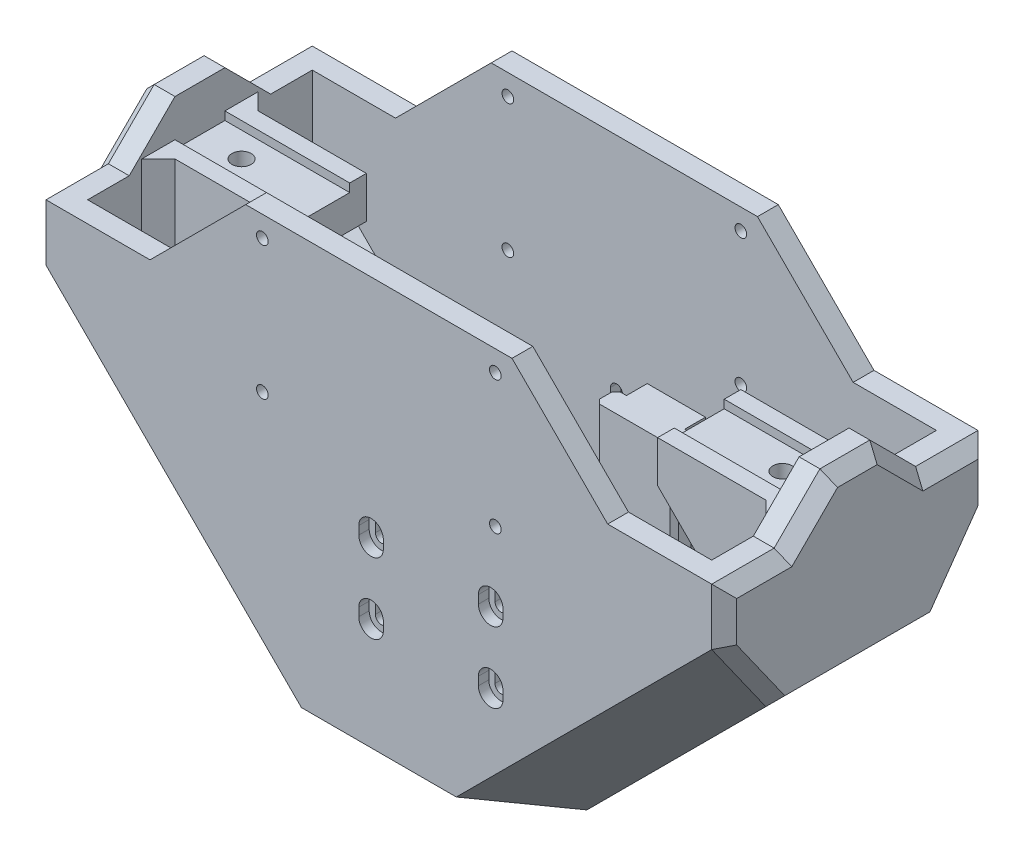
SolidWorks part; units mm, degrees
ref_plane "Front Plane" through (0, 0, 0) normal (0, 0, 1) x (1, 0, 0)
ref_plane "Top Plane" through (0, 0, 0) normal (0, 1, 0) x (1, 0, 0)
ref_plane "Right Plane" through (0, 0, 0) normal (1, 0, 0) x (0, 0, -1)
sketch "Sketch1" plane through (0, 0, 0) normal (0, 1, 0) x (1, 0, 0)
  line L1 (-75, -27) -> (75, -27)
  line L2 (-75, -27) -> (-75, 27)
  line L3 (-75, 27) -> (75, 27)
  line L4 (75, -27) -> (75, 27)
  line L5 (-75, -27) -> (75, 27) construction
  line L6 (-75, 27) -> (75, -27) construction
  point P0 (0, 0)
  dimension "D1" = 150
  dimension "D2" = 54
extrude "Boss-Extrude1" add sketch "Sketch1" along normal blind 70
shell "Shell1" thickness 5
sketch "Sketch2" plane through (80, 0, 0) normal (1, 0, 0) x (0, 0, -1)
  line L0 (-17, 70) -> (-6, 81)
  line L1 (-32, 70) -> (32, 70) construction
  line L2 (-6, 81) -> (6, 81)
  line L3 (6, 81) -> (17, 70)
  line L4 (17, 70) -> (-17, 70)
  line L5 (0, 81) -> (0, 75) construction
  dimension "D1" = 11
  dimension "D2" = 45
  dimension "D3" = 45
  dimension "D4" = 12
extrude "Boss-Extrude2" add sketch "Sketch2" against normal blind 5
sketch "Sketch4" plane through (0, 0, -32) normal (0, 0, -1) x (-1, 0, 0)
  line L0 (-55, 70) -> (-32, 93)
  line L1 (-80, 70) -> (80, 70) construction
  line L2 (-32, 93) -> (32, 93)
  line L3 (32, 93) -> (55, 70)
  line L4 (55, 70) -> (-55, 70)
  line L5 (0, 93) -> (0, 70) construction
  line L6 (-80, 70) -> (-80, -5) construction
  dimension "D1" = 23
  dimension "D2" = 25
  dimension "D3" = 45
extrude "Boss-Extrude3" add sketch "Sketch4" against normal blind 5
sketch "Sketch3" plane through (0, 0, -32) normal (0, 0, -1) x (-1, 0, 0)
  line L1 (-28, 56) -> (28, 56) construction
  line L2 (-28, 56) -> (-28, 88) construction
  line L3 (-28, 88) -> (28, 88) construction
  line L4 (28, 56) -> (28, 88) construction
  line L5 (-28, 56) -> (28, 88) construction
  line L6 (-28, 88) -> (28, 56) construction
  line L7 (32, 93) -> (-32, 93) construction
  circle A0 centre (-28, 88) radius 1.4
  circle A1 centre (-28, 56) radius 1.4
  circle A2 centre (28, 88) radius 1.4
  circle A3 centre (28, 56) radius 1.4
  point P0 (0, 72)
  dimension "D1" = 2.8
  dimension "D2" = 56
  dimension "D3" = 32
  dimension "D4" = 5
extrude "Cut-Extrude1" cut sketch "Sketch3" against normal blind 6
mirror "Mirror4" about plane through (0, 0, 0) normal (0, 0, 1) of "Boss-Extrude3", "Cut-Extrude1"
mirror "Mirror5" about plane through (0, 0, 0) normal (1, 0, 0) of "Boss-Extrude2"
sketch "Sketch5" plane through (0, 0, 0) normal (0, 0, 1) x (1, 0, 0)
  line L0 (-75, 70) -> (-45, 70)
  line L1 (-45, 70) -> (-45, 62)
  line L2 (-45, 62) -> (-75, 32)
  line L4 (-75, 32) -> (-75, 70)
  line L5 (-75, 81) -> (-75, 70) construction
  line L6 (-80, 70) -> (-55, 70) construction
  dimension "D1" = 30
  dimension "D2" = 8
  dimension "D3" = 45
extrude "Boss-Extrude4" add sketch "Sketch5" along normal mid plane 20
sketch "Sketch9" plane through (0, 70, 0) normal (0, 1, 0) x (1, 0, 0)
  line L4 (-45, 10) -> (-75, 10)
  line L5 (-75, 10) -> (-75, -10)
  line L6 (-75, -10) -> (-45, -10)
  line L7 (-45, -10) -> (-45, 10)
  line L8 (-45, 10) -> (-75, 10)
  line L10 (-75, -10) -> (-45, -10)
  line L11 (-45, -10) -> (-45, 10)
  line L13 (-75, 10) -> (-75, -10)
  dimension "D1" = 0
extrude "Boss-Extrude6" add sketch "Sketch9" along normal blind 2
sketch "Sketch10" plane through (-75, 0, 0) normal (1, 0, 0) x (0, 0, -1)
  line L0 (-10, 72) -> (10, 72) construction
  line L1 (-6, 72) -> (6, 72)
  line L2 (-6, 72) -> (-6, 70)
  line L3 (-6, 70) -> (6, 70)
  line L4 (6, 72) -> (6, 70)
  line L5 (-6, 72) -> (6, 70) construction
  line L6 (-6, 70) -> (6, 72) construction
  point P0 (0, 71)
  dimension "D1" = 2
  dimension "D2" = 12
extrude "Cut-Extrude2" cut sketch "Sketch10" along normal up to next
sketch "Sketch11" plane through (0, 70, 0) normal (0, 1, 0) x (1, 0, 0)
  line L1 (-75, 6) -> (-75, -6) construction
  circle A0 centre (-65, 0) radius 2.3
  dimension "D1" = 4.6
  dimension "D2" = 10
extrude "Cut-Extrude3" cut sketch "Sketch11" against normal blind 6
mirror "Mirror24" about plane through (0, 0, 0) normal (1, 0, 0) of "Cut-Extrude2", "Boss-Extrude4", "Boss-Extrude6", "Cut-Extrude3"
chamfer "Chamfer3" distance 40 angle 45 2 edges at (75, 0, 0) (-75, 0, 0)
chamfer "Chamfer5" distance 43 angle 45 2 edges at (-80, -5, 0) (80, -5, 0)
chamfer "Chamfer11" distance 10 angle 45 4 edges at (55, 20, 27) (55, 20, -27) (-55, 20, -27) (-55, 20, 27)
chamfer "Chamfer12" distance 13 angle 45 4 edges at (-58.5, 16.5, -32) (58.5, 16.5, -32) (-58.5, 16.5, 32) (58.5, 16.5, 32)
chamfer "Chamfer13" distance 4 angle 45 8 edges at (-75, 56, -10) (-75, 56, 10) (75, 56, 10) (75, 56, -10) (73, 38, -10) (73, 38, 10) (-73, 38, 10) (-73, 38, -10)
sketch "Sketch16" plane through (80, 0, 0) normal (1, 0, 0) x (0, 0, -1)
  line L10 (-19, 38) -> (19, 38)
  line L11 (19, 38) -> (32, 56.3848)
  line L12 (32, 56.3848) -> (32, 70)
  line L13 (32, 70) -> (17, 70)
  line L14 (17, 70) -> (6, 81)
  line L15 (6, 81) -> (-6, 81)
  line L16 (-6, 81) -> (-17, 70)
  line L17 (-17, 70) -> (-32, 70)
  line L18 (-32, 70) -> (-32, 56.3848)
  line L19 (-32, 56.3848) -> (-19, 38)
  line L20 (-19, 38) -> (19, 38)
  line L21 (19, 38) -> (32, 56.3848)
  line L22 (32, 56.3848) -> (32, 70)
  line L23 (32, 70) -> (17, 70)
  line L24 (17, 70) -> (6, 81)
  line L25 (6, 81) -> (-6, 81)
  line L26 (-6, 81) -> (-17, 70)
  line L27 (-17, 70) -> (-32, 70)
  line L28 (-32, 70) -> (-32, 56.3848)
  line L29 (-32, 56.3848) -> (-19, 38)
  dimension "D1" = 0
extrude "Boss-Extrude10" add sketch "Sketch16" along normal blind 3
chamfer "Chamfer14" distance 3 angle 45 10 edges at (83, 63.1924, 32) (83, 70, 24.5) (83, 75.5, 11.5) (83, 81, 0) (83, 75.5, -11.5) (83, 70, -24.5) (83, 63.1924, -32) (83, 47.1924, -25.5) (83, 38, 0) (83, 47.1924, 25.5)
mirror "Mirror28" about plane through (0, 0, 0) normal (1, 0, 0) of "Chamfer14", "Boss-Extrude10"
sketch "Sketch17" plane through (0, 0, 0) normal (0, 1, 0) x (1, 0, 0)
  line L0 (-32, -27) -> (32, -27) construction
  line L1 (5.5, -27) -> (19.5, -27)
  line L2 (5.5, -27) -> (5.5, -22)
  line L3 (5.5, -22) -> (19.5, -22)
  line L4 (19.5, -27) -> (19.5, -22)
  line L5 (5.5, -27) -> (19.5, -22) construction
  line L6 (5.5, -22) -> (19.5, -27) construction
  line L7 (3, -22) -> (22, -22)
  line L8 (3, -22) -> (3, -17)
  line L9 (3, -17) -> (22, -17)
  line L10 (22, -22) -> (22, -17)
  line L11 (3, -22) -> (22, -17) construction
  line L12 (3, -17) -> (22, -22) construction
  point P0 (12.5, -24.5)
  point P5 (12.5, -19.5)
  line M10 (-20.8579, -27) -> (20.8579, -27)
  dimension "D1" = 19
  dimension "D2" = 14
  dimension "D3" = 5
  dimension "D4" = 12.5
extrude "Boss-Extrude11" add sketch "Sketch17" along normal blind 45 contours L7 L10 L9 L8 L3 | L4 L3 L2 M10
sketch "Sketch20" plane through (0, 0, 0) normal (0, 1, 0) x (1, 0, 0)
  line L0 (22, -22) -> (22, -17) construction
  line L1 (3, -17) -> (22, -17)
  line L2 (3, -17) -> (3, -12)
  line L3 (3, -12) -> (22, -12)
  line L4 (22, -17) -> (22, -12)
  dimension "D1" = 5
extrude "Boss-Extrude14" add sketch "Sketch20" along normal blind 8
mirror "Mirror29" about plane through (0, 0, 0) normal (0, 0, 1) of "Boss-Extrude14", "Boss-Extrude11"
sketch "Sketch22" plane through (0, 0, -27) normal (0, 0, 1) x (1, 0, 0)
  line L0 (5.5, 0) -> (-20.8579, 0) construction
  line L1 (-1.875, 21.8) -> (26.875, 21.8) construction
  line L2 (-1.875, 21.8) -> (-1.875, 38.8) construction
  line L3 (-1.875, 38.8) -> (26.875, 38.8) construction
  line L4 (26.875, 21.8) -> (26.875, 38.8) construction
  line L5 (-1.875, 21.8) -> (26.875, 38.8) construction
  line L6 (-1.875, 38.8) -> (26.875, 21.8) construction
  line L7 (3, 45) -> (22, 45) construction
  line L8 (-1.875, 37.8) -> (-1.875, 39.8) construction
  line L9 (-3.325, 37.8) -> (-3.325, 39.8)
  line L10 (-0.425, 37.8) -> (-0.425, 39.8)
  line L11 (12.5, 38.8) -> (12.5, 30.3) construction
  line L12 (12.5, 30.3) -> (-1.875, 30.3) construction
  line L13 (26.875, 37.8) -> (26.875, 39.8) construction
  line L14 (28.325, 37.8) -> (28.325, 39.8)
  line L15 (25.425, 37.8) -> (25.425, 39.8)
  line L16 (-1.875, 22.8) -> (-1.875, 20.8) construction
  line L17 (-3.325, 22.8) -> (-3.325, 20.8)
  line L18 (-0.425, 22.8) -> (-0.425, 20.8)
  line L19 (26.875, 22.8) -> (26.875, 20.8) construction
  line L20 (28.325, 22.8) -> (28.325, 20.8)
  line L21 (25.425, 22.8) -> (25.425, 20.8)
  arc A4 (-3.325, 37.8) -> (-0.425, 37.8) centre (-1.875, 37.8) ccw
  arc A5 (-0.425, 39.8) -> (-3.325, 39.8) centre (-1.875, 39.8) ccw
  arc A6 (28.325, 37.8) -> (25.425, 37.8) centre (26.875, 37.8) cw
  arc A7 (25.425, 39.8) -> (28.325, 39.8) centre (26.875, 39.8) cw
  arc A8 (-3.325, 22.8) -> (-0.425, 22.8) centre (-1.875, 22.8) cw
  arc A9 (-0.425, 20.8) -> (-3.325, 20.8) centre (-1.875, 20.8) cw
  arc A10 (28.325, 22.8) -> (25.425, 22.8) centre (26.875, 22.8) ccw
  arc A11 (25.425, 20.8) -> (28.325, 20.8) centre (26.875, 20.8) ccw
  point P0 (12.5, 30.3)
  point P7 (12.5, 45)
  point P11 (-1.875, 38.8)
  point P22 (26.875, 38.8)
  point P29 (-1.875, 21.8)
  point P36 (26.875, 21.8)
  dimension "D4" = 1.45
  dimension "D1" = 21.8
  dimension "D2" = 28.75
  dimension "D3" = 17
  dimension "D5" = 2
extrude "Cut-Extrude4" cut sketch "Sketch22" against normal blind 2.5
sketch "Sketch23" plane through (0, 0, -29.5) normal (0, 0, 1) x (1, 0, 0)
  line L6 (29.825, 37.8) -> (29.825, 39.8)
  line L7 (23.925, 39.8) -> (23.925, 37.8)
  line L8 (29.825, 37.8) -> (29.825, 39.8)
  line L9 (23.925, 39.8) -> (23.925, 37.8)
  line L12 (1.075, 37.8) -> (1.075, 39.8)
  line L13 (-4.825, 39.8) -> (-4.825, 37.8)
  line L14 (1.075, 37.8) -> (1.075, 39.8)
  line L15 (-4.825, 39.8) -> (-4.825, 37.8)
  line L18 (-4.825, 22.8) -> (-4.825, 20.8)
  line L19 (1.075, 20.8) -> (1.075, 22.8)
  line L20 (-4.825, 22.8) -> (-4.825, 20.8)
  line L21 (1.075, 20.8) -> (1.075, 22.8)
  line L24 (23.925, 22.8) -> (23.925, 20.8)
  line L25 (29.825, 20.8) -> (29.825, 22.8)
  line L26 (23.925, 22.8) -> (23.925, 20.8)
  line L27 (29.825, 20.8) -> (29.825, 22.8)
  arc A6 (23.925, 37.8) -> (29.825, 37.8) centre (26.875, 37.8) ccw
  arc A7 (29.825, 39.8) -> (23.925, 39.8) centre (26.875, 39.8) ccw
  arc A8 (23.925, 37.8) -> (29.825, 37.8) centre (26.875, 37.8) ccw
  arc A9 (29.825, 39.8) -> (23.925, 39.8) centre (26.875, 39.8) ccw
  arc A12 (-4.825, 37.8) -> (1.075, 37.8) centre (-1.875, 37.8) ccw
  arc A13 (1.075, 39.8) -> (-4.825, 39.8) centre (-1.875, 39.8) ccw
  arc A14 (-4.825, 37.8) -> (1.075, 37.8) centre (-1.875, 37.8) ccw
  arc A15 (1.075, 39.8) -> (-4.825, 39.8) centre (-1.875, 39.8) ccw
  arc A18 (1.075, 22.8) -> (-4.825, 22.8) centre (-1.875, 22.8) ccw
  arc A19 (-4.825, 20.8) -> (1.075, 20.8) centre (-1.875, 20.8) ccw
  arc A20 (1.075, 22.8) -> (-4.825, 22.8) centre (-1.875, 22.8) ccw
  arc A21 (-4.825, 20.8) -> (1.075, 20.8) centre (-1.875, 20.8) ccw
  arc A24 (29.825, 22.8) -> (23.925, 22.8) centre (26.875, 22.8) ccw
  arc A25 (23.925, 20.8) -> (29.825, 20.8) centre (26.875, 20.8) ccw
  arc A26 (29.825, 22.8) -> (23.925, 22.8) centre (26.875, 22.8) ccw
  arc A27 (23.925, 20.8) -> (29.825, 20.8) centre (26.875, 20.8) ccw
  dimension "D1" = 1.5
  dimension "D2" = 1.5
  dimension "D3" = 1.5
  dimension "D4" = 1.5
extrude "Cut-Extrude5" cut sketch "Sketch23" against normal up to next contours A8 L8 A9 L9 | A14 L14 A15 L15 | A20 L20 A21 L21 | A26 L26 A27 L27
mirror "Mirror30" about plane through (0, 0, 0) normal (0, 0, 1) of "Cut-Extrude5", "Cut-Extrude4"
sketch "Sketch24" plane through (17.5, -17.5, 0) normal (-0.7071, 0.7071, 0) x (0, 0, 1)
  line L0 (17, 24.7487) -> (-17, 24.7487) construction
  line L1 (-7.5, 29.7487) -> (7.5, 29.7487)
  line L2 (-7.5, 29.7487) -> (-7.5, 37.7487)
  line L3 (-7.5, 37.7487) -> (7.5, 37.7487)
  line L4 (7.5, 29.7487) -> (7.5, 37.7487)
  line L5 (-7.5, 29.7487) -> (7.5, 37.7487) construction
  line L6 (-7.5, 37.7487) -> (7.5, 29.7487) construction
  point P0 (0, 33.7487)
  dimension "D1" = 5
  dimension "D2" = 15
  dimension "D3" = 8
extrude "Cut-Extrude6" cut sketch "Sketch24" against normal up to next
chamfer "Chamfer18" distance 4 angle 45 4 edges at (22, 0, 17) (3, 0, -17) (3, 0, 17) (22, 0, -17)
chamfer "Chamfer19" distance 1 angle 45 8 edges at (3, 24.5, 22) (22, 24.5, 22) (22, 26.5, 17) (3, 26.5, 17) (3, 24.5, -22) (3, 26.5, -17) (22, 26.5, -17) (22, 24.5, -22)
chamfer "Chamfer20" distance 2 angle 45 4 edges at (40.2855, 1.7855, -7.5) (40.2855, 1.7855, 7.5) (45.9424, 7.4424, 7.5) (45.9424, 7.4424, -7.5)
